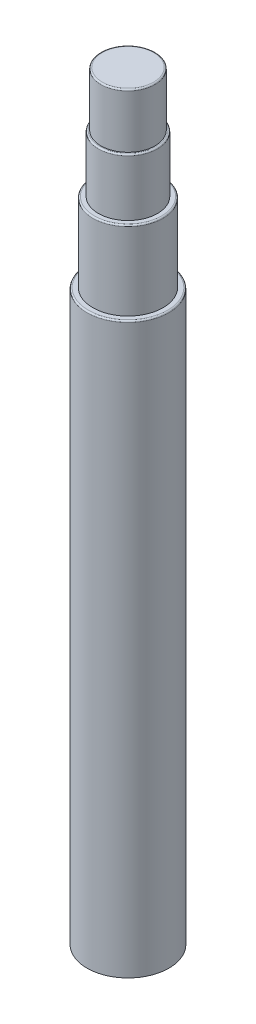
SolidWorks part; units mm, degrees
ref_plane "Front Plane" through (0, 0, 0) normal (0, 0, 1) x (1, 0, 0)
ref_plane "Top Plane" through (0, 0, 0) normal (0, 1, 0) x (1, 0, 0)
ref_plane "Right Plane" through (0, 0, 0) normal (1, 0, 0) x (0, 0, -1)
sketch "Sketch1" plane through (0, 0, 0) normal (0, 1, 0) x (1, 0, 0)
  circle A0 centre (0, 0) radius 28.575
  dimension "D1" = 57.15
extrude "Boss-Extrude1" add sketch "Sketch1" along normal blind 397
sketch "Sketch2" plane through (0, 397, 0) normal (0, 1, 0) x (1, 0, 0)
  circle A0 centre (0, 0) radius 24.5
  dimension "D1" = 49
extrude "Boss-Extrude2" add sketch "Sketch2" along normal blind 55
sketch "Sketch3" plane through (0, 452, 0) normal (0, 1, 0) x (1, 0, 0)
  circle A0 centre (0, 0) radius 20.64
  dimension "D1" = 41.28
extrude "Boss-Extrude3" add sketch "Sketch3" along normal blind 40
sketch "Sketch4" plane through (0, 492, 0) normal (0, 1, 0) x (1, 0, 0)
  circle A0 centre (0, 0) radius 18.9
  dimension "D1" = 37.8
extrude "Boss-Extrude4" add sketch "Sketch4" along normal blind 38
fillet "Fillet1" radius 1 4 edges at (0, 397, 28.575) (0, 452, 24.5) (0, 492, 20.64) (0, 530, 18.9)
